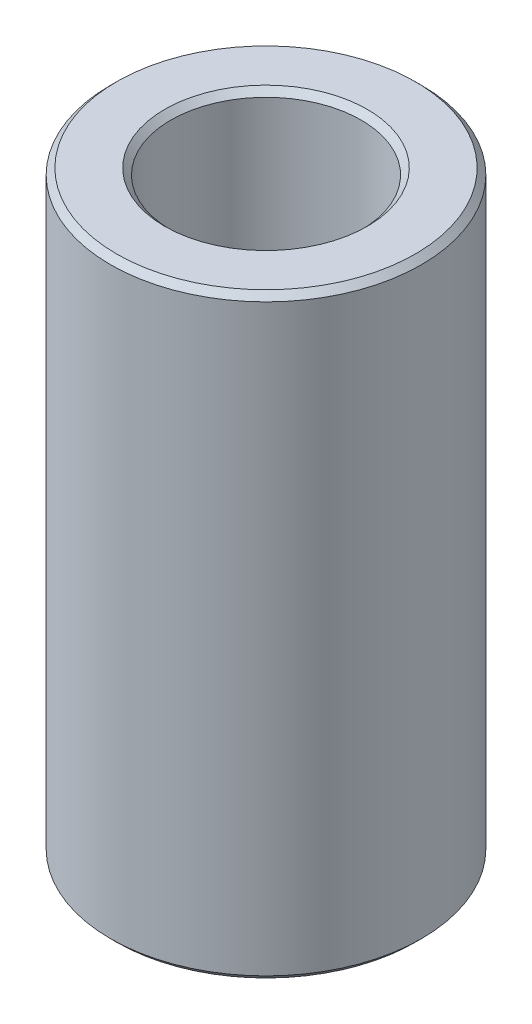
SolidWorks part; units mm, degrees
ref_plane "Front Plane" through (0, 0, 0) normal (0, 0, 1) x (1, 0, 0)
ref_plane "Top Plane" through (0, 0, 0) normal (0, 1, 0) x (1, 0, 0)
ref_plane "Right Plane" through (0, 0, 0) normal (1, 0, 0) x (0, 0, -1)
sketch "Sketch1" plane through (0, 0, 0) normal (0, 1, 0) x (1, 0, 0)
  circle A0 centre (0, 0) radius 42.5
  dimension "SLEEVE_OD" = 85
extrude "Boss-Extrude1" add sketch "Sketch1" along normal blind 162.9328
sketch "Sketch2" plane through (0, 0, 0) normal (0, 1, 0) x (1, 0, 0)
  circle A0 centre (0, 0) radius 26.0155
  dimension "BORE_D" = 52.0309
extrude "Cut-Extrude1" cut sketch "Sketch2" along normal through all
chamfer "Chamfer1" distance 1.6848 angle 45 4 edges at (0, 162.9328, 26.0155) (0, 0, 26.0155) (0, 0, 42.5) (0, 162.9328, 42.5)
